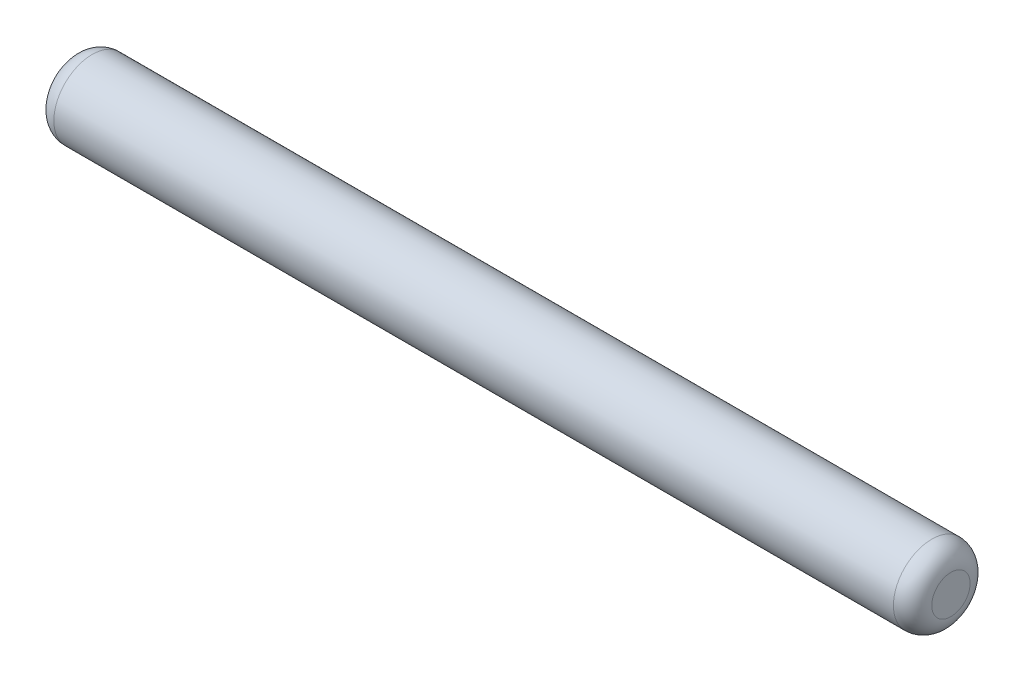
SolidWorks part; units mm, degrees
ref_plane "Front Plane" through (0, 0, 0) normal (0, 0, 1) x (1, 0, 0)
ref_plane "Top Plane" through (0, 0, 0) normal (0, 1, 0) x (1, 0, 0)
ref_plane "Right Plane" through (0, 0, 0) normal (1, 0, 0) x (0, 0, -1)
sketch "Sketch1" plane through (0, 0, 0) normal (1, 0, 0) x (0, 0, -1)
  circle A0 centre (0, 0) radius 1
  dimension "D1" = 2
extrude "Boss-Extrude1" add sketch "Sketch1" along normal blind 11.45 and the other way blind 11.45
fillet "Fillet1" radius 0.5 2 edges at (-11.45, 0, -1) (11.45, 0, -1)
